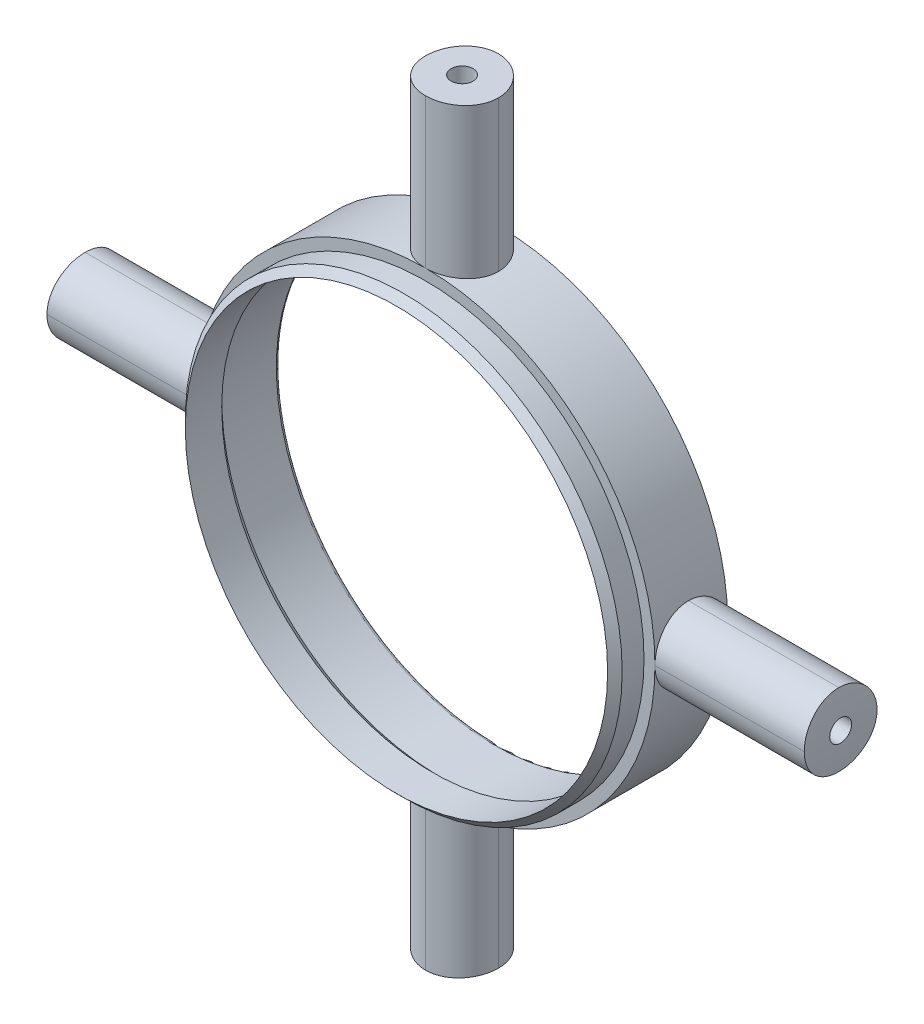
SolidWorks part; units mm, degrees
note: '?' marks a value the reader was unsure of.
ref_plane "Front Plane" through (0, 0, 0) normal (0, 0, 1) x (1, 0, 0)
ref_plane "Top Plane" through (0, 0, 0) normal (0, 1, 0) x (1, 0, 0)
ref_plane "Right Plane" through (0, 0, 0) normal (1, 0, 0) x (0, 0, -1)
sketch "Sketch1" plane through (0, 0, 0) normal (0, 0, 1) x (1, 0, 0)
  circle A0 centre (0, 0) radius 30
  circle A1 centre (0, 0) radius 31.5
  dimension "D1" = 60
  dimension "D2" = 1.5
extrude "Boss-Extrude1" add sketch "Sketch1" along normal blind 10
sketch "Sketch2" plane through (0, 0, 10) normal (0, 0, 1) x (1, 0, 0)
  circle A1 centre (0, 0) radius 31.5
  circle A2 centre (0, 0) radius 31.5
  dimension "D1" = 0
ref_plane "Plane1" through (0, 0, 5) normal (0, 0, 1) x (1, 0, 0)
ref_plane "Plane2" through (-31.5, 0, 0) normal (-1, 0, 0) x (0, 0, 1)
sketch "Sketch4" plane through (-31.5, 0, 0) normal (-1, 0, 0) x (0, 0, 1)
  line L0 (0, 0) -> (10, 0) construction
  line L1 (10, -31.5) -> (10, 31.5) construction
  line L3 (0, -5) -> (10, -5)
  line L4 (0, -5) -> (0, 5)
  line L5 (0, 5) -> (10, 5)
  line L6 (10, -5) -> (10, 5)
  line L7 (0, -5) -> (10, 5) construction
  line L8 (0, 5) -> (10, -5) construction
  point P5 (5, 0)
  dimension "D1" = 10
  dimension "D2" = 10
extrude "Boss-Extrude3" add sketch "Sketch4" along normal blind 30 and the other way up to surface
ref_axis "Axis1" through (0, 0, 10) along (0, 0, -1)?
fillet "Fillet1" radius 5 4 edges at (-46.3003, 5, 10) (-46.3003, -5, 10) (-46.3003, 5, 0) (-46.3003, -5, 0)
sketch "Sketch6" plane through (-61.5, 0, 0) normal (-1, 0, 0) x (0, 0, 1)
  circle A0 centre (5, 0) radius 1.5
  dimension "D1" = 3
extrude "Cut-Extrude8" cut sketch "Sketch6" against normal blind 30
pattern_circular "CirPattern1" count 4 over 360 about axis through (0, 0, 0) along (0, 0, 1) of "Boss-Extrude3", "Fillet1", "Cut-Extrude8"
sketch "Sketch5" plane through (0, 0, 10) normal (0, 0, 1) x (1, 0, 0)
  circle A0 centre (0, 0) radius 52
  circle A1 centre (0, 0) radius 69.0912
  dimension "D1" = 104
extrude "Cut-Extrude7" cut sketch "Sketch5" against normal blind 200
sketch "Sketch7" plane through (0, 0, 10) normal (0, 0, 1) x (1, 0, 0)
  circle A0 centre (0, 0) radius 30 construction
  circle A1 centre (0, 0) radius 30
  circle A2 centre (0, 0) radius 29
  arc A4 (-31.5, 0) -> (0, -31.5) centre (0, 0) ccw
  arc A5 (0, -31.5) -> (31.5, 0) centre (0, 0) ccw
  arc A6 (31.5, 0) -> (0, 31.5) centre (0, 0) ccw
  arc A7 (0, 31.5) -> (-31.5, 0) centre (0, 0) ccw
  arc A8 (-31.5, 0) -> (0, -31.5) centre (0, 0) ccw
  arc A9 (0, -31.5) -> (31.5, 0) centre (0, 0) ccw
  arc A10 (31.5, 0) -> (0, 31.5) centre (0, 0) ccw
  arc A11 (0, 31.5) -> (-31.5, 0) centre (0, 0) ccw
  circle M9 centre (0, 0) radius 30
  dimension "D1" = 0
  dimension "D2" = 1
extrude "Boss-Extrude4" add sketch "Sketch7" along normal blind 4 and the other way blind 2 contours A2 M9 | A1
chamfer "Chamfer1" distance 1 angle 45 2 edges at (29, 0, 8) (30, 0, 14)
fillet "Fillet2" radius 0.5 1 edges at (30, 0, 0)
